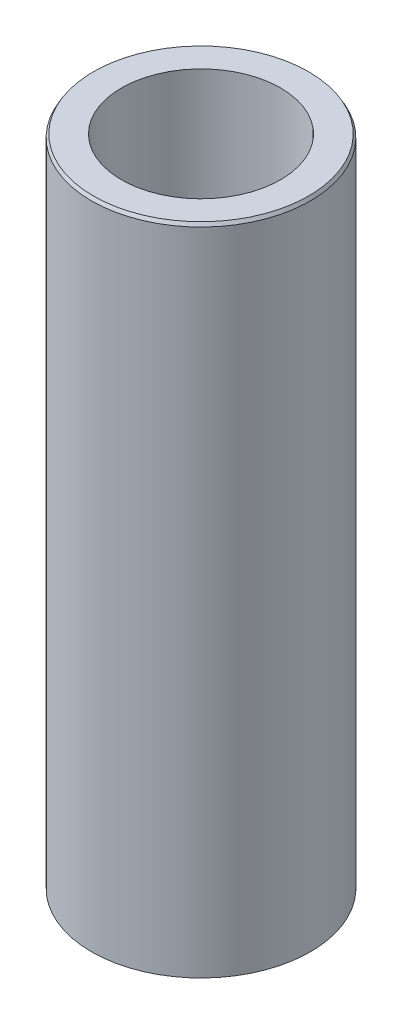
SolidWorks part; units mm, degrees
ref_plane "Front Plane" through (0, 0, 0) normal (0, 0, 1) x (1, 0, 0)
ref_plane "Top Plane" through (0, 0, 0) normal (0, 1, 0) x (1, 0, 0)
ref_plane "Right Plane" through (0, 0, 0) normal (1, 0, 0) x (0, 0, -1)
sketch "Sketch1" plane through (0, 0, 0) normal (0, 1, 0) x (1, 0, 0)
  circle A0 centre (0, 0) radius 52.5
  dimension "SHAFT_OD" = 105
extrude "Boss-Extrude1" add sketch "Sketch1" along normal blind 314.2072
sketch "Sketch2" plane through (0, 0, 0) normal (0, 1, 0) x (1, 0, 0)
  circle A0 centre (0, 0) radius 38.1459
  dimension "BORE_D" = 76.2918
extrude "Cut-Extrude1" cut sketch "Sketch2" along normal through all
chamfer "Chamfer1" distance 1.5711 angle 30 2 edges at (0, 314.2072, 52.5) (0, 0, 52.5) first distance on face at (0, 314.2072, 52.5) first distance on face at (0, 0, 38.1459)
